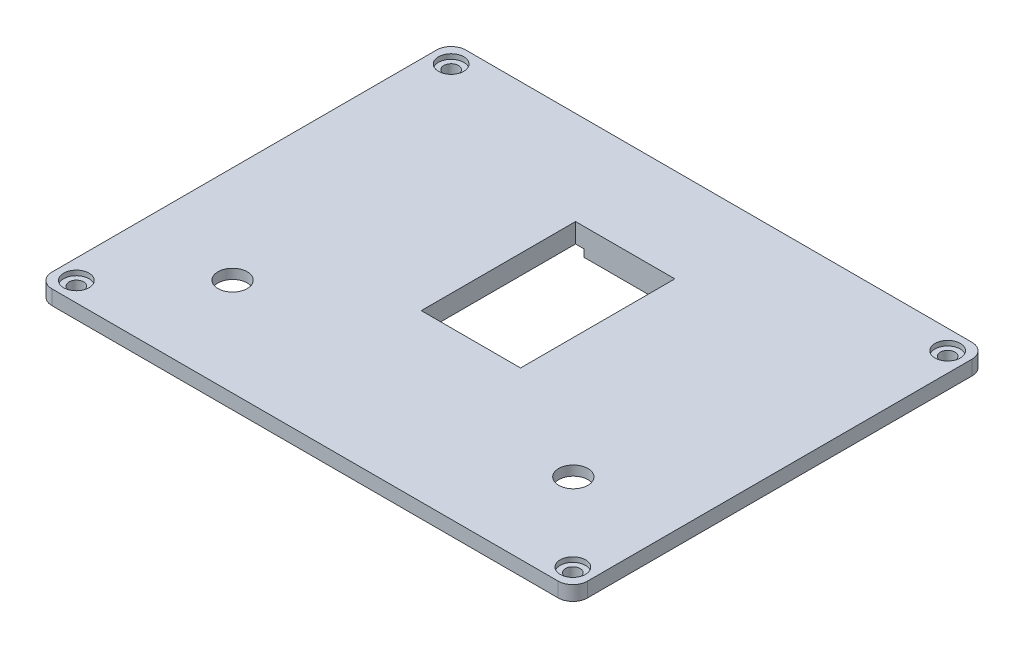
SolidWorks part; units mm, degrees
note: The reader was unsure of these and kept them because the rebuilt part matched: shared geometry of "Sketch3<2>", "Sketch17<3>", "Sketch18<4>".
ref_plane "Front Plane" through (0, 0, 0) normal (0, 0, 1) x (1, 0, 0)
ref_plane "Top Plane" through (0, 0, 0) normal (0, 1, 0) x (1, 0, 0)
ref_plane "Right Plane" through (0, 0, 0) normal (1, 0, 0) x (0, 0, -1)
sketch "Sketch1" plane through (0, 0, 0) normal (0, 1, 0) x (1, 0, 0)
  line L1 (0, 0) -> (110, 0)
  line L2 (0, 0) -> (0, 85)
  line L3 (0, 85) -> (110, 85)
  line L4 (110, 0) -> (110, 85)
  dimension "D1" = 85
  dimension "D2" = 110
extrude "Boss-Extrude1" add sketch "Sketch1" along normal blind 3
sketch "Sketch2" plane through (0, 0, 0) normal (0, -1, 0) x (1, 0, 0)
  line L14 (104.9, -79.9) -> (104.9, -5.1)
  line L15 (5.1, -79.9) -> (104.9, -79.9)
  line L16 (5.1, -5.1) -> (5.1, -79.9)
  line L17 (104.9, -5.1) -> (5.1, -5.1)
  line L18 (104.9, -79.9) -> (104.9, -5.1)
  line L19 (5.1, -79.9) -> (104.9, -79.9)
  line L20 (5.1, -5.1) -> (5.1, -79.9)
  line L21 (104.9, -5.1) -> (5.1, -5.1)
  circle A0 centre (5.1, -5.1) radius 4
  circle A1 centre (104.9, -5.1) radius 4
  circle A2 centre (104.9, -79.9) radius 4
  circle A3 centre (5.1, -79.9) radius 4
  dimension "D2" = 8
  dimension "D3" = 8
  dimension "D4" = 8
  dimension "D5" = 8
  dimension "D1" = 5.1
extrude "Boss-Extrude2" add sketch "Sketch2" along normal blind 1 contours A3 L19 A2 L18 A1 L21 A0 L20
sketch "Sketch3" plane through (0, 3, 0) normal (0, 1, 0) x (1, 0, 0)
  line L10 (55, 85) -> (55, 0) construction
  line L11 (110, 85) -> (0, 85) construction
  line L12 (0, 0) -> (110, 0) construction
  line L13 (0, 42.5) -> (110, 42.5) construction
  line L14 (106, 4) -> (106, 81)
  line L15 (4, 4) -> (106, 4)
  line L16 (4, 81) -> (4, 4)
  line L17 (106, 81) -> (4, 81)
  line L18 (106, 4) -> (106, 81) construction
  line L19 (4, 4) -> (106, 4) construction
  line L20 (4, 81) -> (4, 4) construction
  line L21 (106, 81) -> (4, 81) construction
  line L22 (0, 85) -> (0, 0) construction
  line L23 (110, 0) -> (110, 85) construction
  circle A0 centre (4, 81) radius 1.5
  circle A1 centre (4, 81) radius 2.6
  circle A2 centre (106, 81) radius 2.6
  circle A3 centre (106, 81) radius 1.5
  circle A4 centre (106, 4) radius 1.5
  circle A5 centre (106, 4) radius 2.6
  circle A6 centre (4, 4) radius 2.6
  circle A7 centre (4, 4) radius 1.5
  dimension "D2" = 3
  dimension "D3" = 5.2
  dimension "D1" = 4
extrude "Cut-Extrude1" cut sketch "Sketch3" against normal blind 1
extrude "Cut-Extrude2" cut sketch "Sketch3<2>" against normal up to next contours A0 | A3 | A4 | A7
sketch "Sketch3<2>" plane through (0, 3, 0) normal (0, 1, 0) x (1, 0, 0) same geometry as "Sketch3"
fillet "Fillet1" radius 3 4 edges at (110, 1.5, -85) (110, 1.5, 0) (0, 1.5, 0) (0, 1.5, -85)
sketch "Sketch14" plane through (0, 0, 0) normal (0, -1, 0) x (1, 0, 0)
  line L4 (55, -3.35) -> (55, -81.65) construction
  line L5 (3.35, -42.5) -> (106.65, -42.5) construction
  line L6 (7.35, -5.1) -> (7.35, -3.35)
  line L7 (5.1, -7.35) -> (3.35, -7.35)
  line L8 (6.5142, -81.65) -> (103.4858, -81.65)
  line L9 (106.65, -78.4858) -> (106.65, -6.5142)
  line L10 (103.4858, -3.35) -> (6.5142, -3.35)
  line L11 (3.35, -6.5142) -> (3.35, -78.4858)
  line L12 (7.35, -81.65) -> (102.65, -81.65)
  line L13 (106.65, -77.65) -> (106.65, -7.35)
  line L14 (102.65, -3.35) -> (7.35, -3.35)
  line L15 (3.35, -7.35) -> (3.35, -77.65)
  line L16 (104.9, -7.35) -> (106.65, -7.35)
  line L17 (102.65, -5.1) -> (102.65, -3.35)
  line L18 (104.9, -77.65) -> (106.65, -77.65)
  line L19 (102.65, -79.9) -> (102.65, -81.65)
  line L20 (5.1, -77.65) -> (3.35, -77.65)
  line L21 (7.35, -79.9) -> (7.35, -81.65)
  arc A8 (6.5142, -81.65) -> (3.35, -78.4858) centre (5.1, -79.9) ccw
  arc A9 (106.65, -78.4858) -> (103.4858, -81.65) centre (104.9, -79.9) ccw
  arc A10 (103.4858, -3.35) -> (106.65, -6.5142) centre (104.9, -5.1) ccw
  arc A11 (3.35, -6.5142) -> (6.5142, -3.35) centre (5.1, -5.1) ccw
  arc A12 (7.35, -79.9) -> (5.1, -77.65) centre (5.1, -79.9) ccw
  arc A13 (104.9, -77.65) -> (102.65, -79.9) centre (104.9, -79.9) ccw
  arc A14 (102.65, -5.1) -> (104.9, -7.35) centre (104.9, -5.1) ccw
  arc A15 (5.1, -7.35) -> (7.35, -5.1) centre (5.1, -5.1) ccw
  dimension "D1" = 1.75
ref_plane "Plane3" through (0, 0, -77.65) normal (0, 0, 1) x (1, 0, 0)
sketch "Sketch15" plane through (0, 0, -77.65) normal (0, 0, 1) x (1, 0, 0)
  line L0 (104.9, 0) -> (106.65, 0) construction
  circle A0 centre (106.65, 0) radius 1.75
  dimension "D1" = 3.5
sweep "Cut-Sweep3" cut profiles "Sketch15" path "Sketch14"
sketch "Sketch17" plane through (0, -1, 0) normal (0, -1, 0) x (1, 0, 0)
  line L0 (55, -5.1) -> (55, -79.9) construction
  line L1 (100.9, -5.1) -> (9.1, -5.1) construction
  line L2 (9.1, -79.9) -> (100.9, -79.9) construction
  circle A0 centre (90, -20.1) radius 3
  circle A1 centre (90, -20.1) radius 6
  circle A2 centre (20, -20.1) radius 6
  circle A3 centre (20, -20.1) radius 3
  dimension "D1" = 6
  dimension "D2" = 12
  dimension "D3" = 35
  dimension "D4" = 15
extrude "Cut-Extrude3" cut sketch "Sketch17" against normal up to next contours A3 | A0
extrude "Cut-Extrude4" cut sketch "Sketch17<3>" against normal blind 2
sketch "Sketch17<3>" plane through (0, -1, 0) normal (0, -1, 0) x (1, 0, 0) same geometry as "Sketch17"
sketch "Sketch18" plane through (0, -1, 0) normal (0, -1, 0) x (1, 0, 0)
  line L0 (55, -5.1) -> (55, -79.9) construction
  line L1 (100.9, -5.1) -> (9.1, -5.1) construction
  line L2 (9.1, -79.9) -> (100.9, -79.9) construction
  line L4 (44.8, -65.7586) -> (65.2, -65.7586)
  line L5 (44.8, -65.7586) -> (44.8, -34.0586)
  line L6 (44.8, -34.0586) -> (65.2, -34.0586)
  line L7 (65.2, -65.7586) -> (65.2, -34.0586)
  line L8 (44.8, -65.7586) -> (65.2, -34.0586) construction
  line L9 (44.8, -34.0586) -> (65.2, -65.7586) construction
  line L10 (46.5, -70.9086) -> (63.5, -70.9086)
  line L11 (46.5, -70.9086) -> (46.5, -28.9086)
  line L12 (46.5, -28.9086) -> (63.5, -28.9086)
  line L13 (63.5, -70.9086) -> (63.5, -28.9086)
  line L14 (46.5, -70.9086) -> (63.5, -28.9086) construction
  line L15 (46.5, -28.9086) -> (63.5, -70.9086) construction
  point P6 (55, -49.9086)
  point P11 (55, -49.9086)
  dimension "D1" = 31.7
  dimension "D2" = 20.4
  dimension "D3" = 17
  dimension "D4" = 42
extrude "Cut-Extrude5" cut sketch "Sketch18" against normal through all contours L6 L7 L4 L5
extrude "Boss-Extrude3" add sketch "Sketch18<4>" along normal blind 1.5 contours L6 L13 L12 L11 | L10 L13 L4 L11
sketch "Sketch18<4>" plane through (0, -1, 0) normal (0, -1, 0) x (1, 0, 0) same geometry as "Sketch18"
sketch "Sketch19" plane through (0, -2.5, 0) normal (0, -1, 0) x (1, 0, 0)
  line L0 (44.8, -49.9086) -> (65.2, -49.9086) construction
  line L1 (44.8, -65.7586) -> (44.8, -34.0586) construction
  line L2 (65.2, -65.7586) -> (65.2, -34.0586) construction
  line L3 (55, -28.9086) -> (55, -70.9086) construction
  line L4 (46.5, -28.9086) -> (63.5, -28.9086) construction
  line L5 (46.5, -70.9086) -> (63.5, -70.9086) construction
  circle A0 centre (55, -31.9086) radius 1
  circle A1 centre (55, -67.9086) radius 1
  dimension "D1" = 2
  dimension "D2" = 18
extrude "Cut-Extrude6" cut sketch "Sketch19" against normal blind 5
fillet "Fillet2" radius 1 4 edges at (46.5, -1.75, -70.9086) (63.5, -1.75, -70.9086) (63.5, -1.75, -28.9086) (46.5, -1.75, -28.9086)
